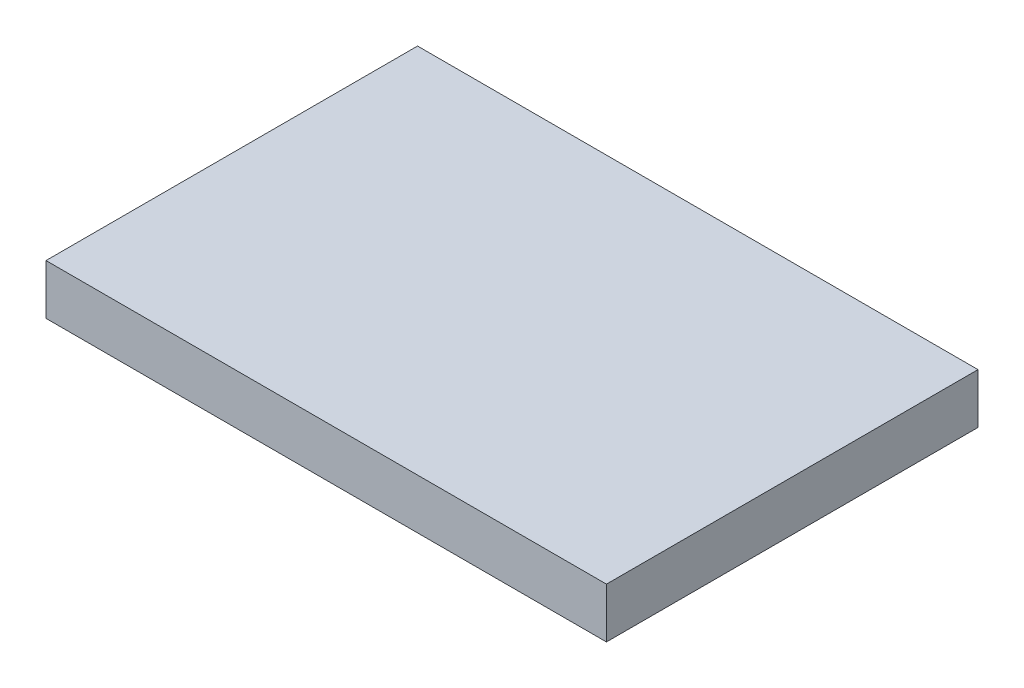
SolidWorks part; units mm, degrees
ref_plane "Front" through (0, 0, 0) normal (0, 0, 1) x (1, 0, 0)
ref_plane "Top" through (0, 0, 0) normal (0, 1, 0) x (1, 0, 0)
ref_plane "Right" through (0, 0, 0) normal (1, 0, 0) x (0, 0, -1)
sketch "Sketch1" plane through (0, 0, 0) normal (0, 1, 0) x (1, 0, 0)
  line L1 (-1447.8, 825.5) -> (1447.8, 825.5)
  line L2 (-1447.8, 825.5) -> (-1447.8, -825.5)
  line L3 (-1447.8, -825.5) -> (1447.8, -825.5)
  line L4 (1447.8, 825.5) -> (1447.8, -825.5)
  line L5 (-1447.8, 825.5) -> (1447.8, -825.5) construction
  line L6 (-1447.8, -825.5) -> (1447.8, 825.5) construction
  point P0 (0, 0)
  dimension "D1" = 2895.6
  dimension "D2" = 1651
extrude "Boss-Extrude1" [suppressed] add sketch "Sketch1" along normal blind 1473.2
sketch "Sketch2" [suppressed] plane through (0, 0, 0) normal (0, -1, 0) x (1, 0, 0)
  line L0 (0, 0) -> (2162.175, 0) construction
  line L1 (1447.8, 825.5) -> (1447.8, -825.5) construction
  line L2 (1752.6, 663.575) -> (2571.75, 663.575)
  line L3 (1752.6, 663.575) -> (1752.6, -663.575)
  line L4 (1752.6, -663.575) -> (2571.75, -663.575)
  line L5 (2571.75, 663.575) -> (2571.75, -663.575)
  line L6 (1752.6, 663.575) -> (2571.75, -663.575) construction
  line L7 (1752.6, -663.575) -> (2571.75, 663.575) construction
  dimension "D1" = 1327.15
  dimension "D2" = 819.15
  dimension "D3" = 304.8
extrude "Boss-Extrude2" [suppressed] add sketch "Sketch2" against normal blind 736.6 separate body
sketch "Sketch3" plane through (0, 0, 0) normal (0, 1, 0) x (-1, 0, 0)
  line L2 (1704.975, 1130.3) -> (-1704.975, 1130.3)
  line L3 (1704.975, 1130.3) -> (1704.975, -1130.3)
  line L4 (1704.975, -1130.3) -> (-1704.975, -1130.3)
  line L5 (-1704.975, 1130.3) -> (-1704.975, -1130.3)
  line L6 (1704.975, 1130.3) -> (-1704.975, -1130.3) construction
  line L7 (1704.975, -1130.3) -> (-1704.975, 1130.3) construction
  point P7 (-2552.9639, 1130.3)
  dimension "D1" = 2260.6
  dimension "D2" = 3409.95
  dimension "D4" = 2260.6
  dimension "D5" = 3409.95
extrude "Boss-Extrude3" add sketch "Sketch3" along normal blind 304.8 separate body
